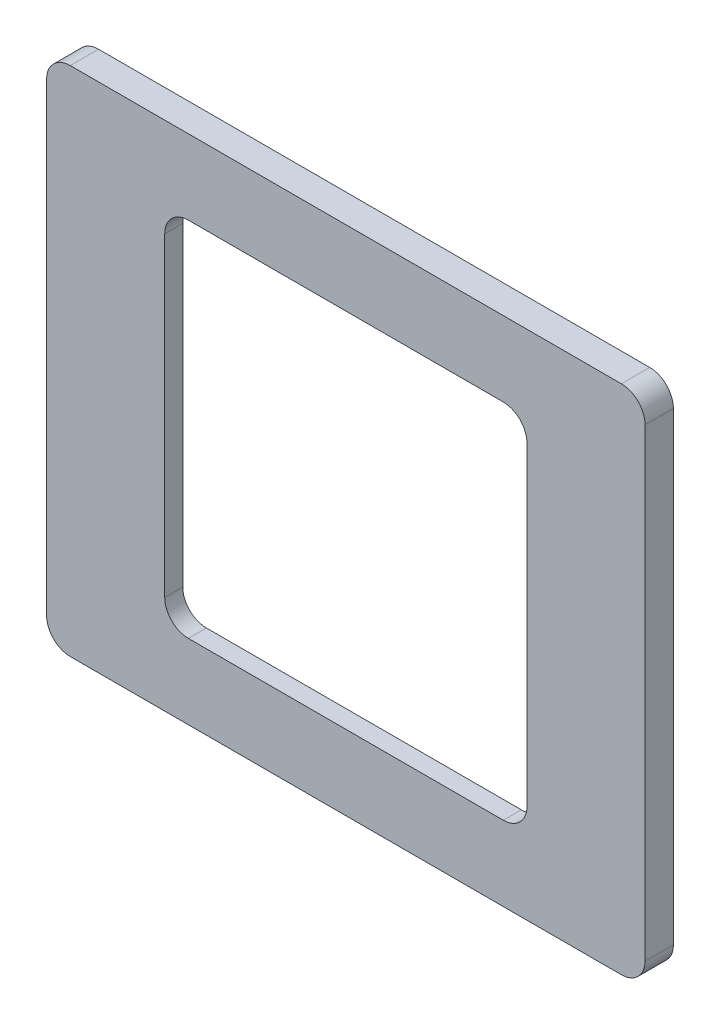
SolidWorks part; units mm, degrees
ref_plane "Front Plane" through (0, 0, 0) normal (0, 0, 1) x (1, 0, 0)
ref_plane "Top Plane" through (0, 0, 0) normal (0, 1, 0) x (1, 0, 0)
ref_plane "Right Plane" through (0, 0, 0) normal (1, 0, 0) x (0, 0, -1)
sketch "Sketch1" plane through (0, 0, 0) normal (0, 1, 0) x (1, 0, 0)
  line L1 (38, 3.6) -> (-38, 3.6)
  line L2 (38, 3.6) -> (38, 0)
  line L3 (-38, 3.6) -> (-38, 0)
  line L5 (0, -1.941) -> (0, 24.0569) construction
  line L9 (-38, 0) -> (38, 0)
  point P19 (0, 0)
  dimension "D2" = 76
  dimension "D5" = 3.6
extrude "Boss-Extrude1" add sketch "Sketch1" along normal blind 65
ref_plane "Plane1" through (0, 0, -3.6) normal (0, 0, -1) x (-1, 0, 0)
sketch "Sketch2" plane through (0, 0, -3.6) normal (0, 0, -1) x (-1, 0, 0)
  line L0 (0, 1.98) -> (0, -1.98) construction
  line L1 (25.145, 7.355) -> (-25.145, 7.355)
  line L2 (25.145, 7.355) -> (25.145, 57.645)
  line L3 (25.145, 57.645) -> (-25.145, 57.645)
  line L4 (-25.145, 7.355) -> (-25.145, 57.645)
  line L5 (25.145, 7.355) -> (-25.145, 57.645) construction
  line L6 (25.145, 57.645) -> (-25.145, 7.355) construction
  line L7 (0, 0) -> (0, 65) construction
  line L8 (-38, 65) -> (38, 65) construction
  point P0 (0, 32.5)
  point P13 (0, 32.5)
  dimension "D1" = 50.29
extrude "Cut-Extrude1" cut sketch "Sketch2" against normal blind 1.31
sketch "Sketch3" plane through (0, 0, -2.29) normal (0, 0, -1) x (-1, 0, 0)
  line L1 (23, 9.5) -> (-23, 9.5)
  line L2 (23, 9.5) -> (23, 55.5)
  line L3 (23, 55.5) -> (-23, 55.5)
  line L4 (-23, 9.5) -> (-23, 55.5)
  line L5 (23, 9.5) -> (-23, 55.5) construction
  line L6 (23, 55.5) -> (-23, 9.5) construction
  point P0 (0, 32.5)
  dimension "D1" = 46
extrude "Cut-Extrude2" cut sketch "Sketch3" against normal through all
fillet "Fillet1" radius 3 8 edges at (-23, 55.5, -1.145) (23, 55.5, -1.145) (23, 9.5, -1.145) (-23, 9.5, -1.145) (38, 0, -1.8) (-38, 0, -1.8) (-38, 65, -1.8) (38, 65, -1.8)
